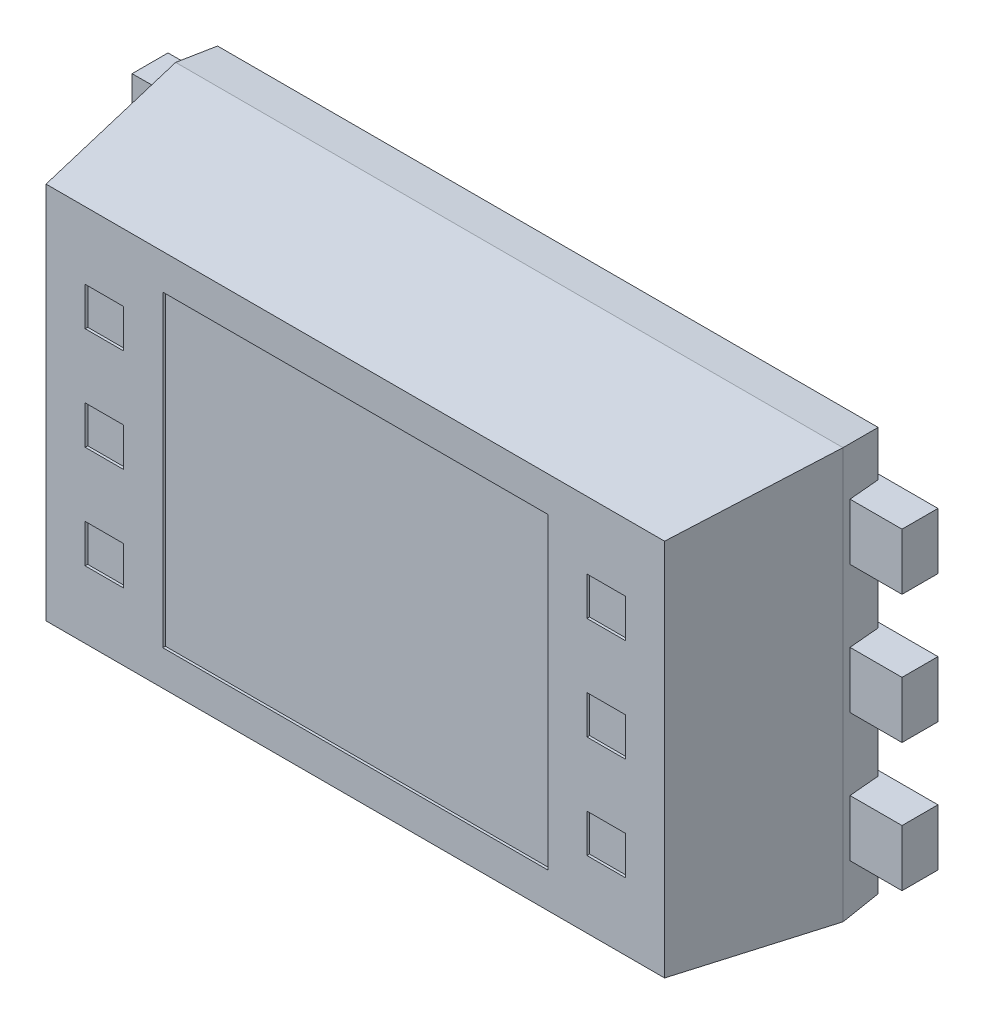
SolidWorks part; units mm, degrees
ref_plane "Спереди" through (0, 0, 0) normal (0, 0, 1) x (1, 0, 0)
ref_plane "Сверху" through (0, 0, 0) normal (0, 1, 0) x (1, 0, 0)
ref_plane "Справа" through (0, 0, 0) normal (1, 0, 0) x (0, 0, -1)
sketch "Эскиз1" plane through (0, 0, 0) normal (0, 0, 1) x (1, 0, 0)
  line L1 (0, 0) -> (2.6, 0)
  line L2 (0, 0) -> (0, 1.6)
  line L3 (0, 1.6) -> (2.6, 1.6)
  line L4 (2.6, 0) -> (2.6, 1.6)
  dimension "D1" = 2.6
  dimension "D2" = 1.6
extrude "Бобышка-Вытянуть1" add sketch "Эскиз1" along normal blind 0.6 and the other way blind 0.15 draft 5
chamfer "Фаска1" distance 0.6 angle 9 2 edges at (0, 0.8, 0.6) (2.6, 0.8, 0.6)
chamfer "Фаска2" distance 0.6 angle 6 2 edges at (1.3, 0, 0.6) (1.3, 1.6, 0.6)
sketch "Эскиз4" plane through (0, 0, -0.15) normal (0, 0, -1) x (-1, 0, 0)
  line L1 (-2.8, 0.8) -> (-2.8, 0.69)
  line L2 (-2.8, 0.69) -> (-2.53, 0.69)
  line L4 (-0.07, 0.41) -> (0.2, 0.41)
  line L5 (-2.8, 0.8) -> (-2.8, 0.91)
  line L6 (-2.53, 0.69) -> (-2.53, 0.91)
  line L7 (-2.53, 0.91) -> (-2.8, 0.91)
  line L9 (-2.8, 0.3) -> (-2.8, 0.19)
  line L10 (-2.8, 0.19) -> (-2.53, 0.19)
  line L11 (-2.8, 0.3) -> (-2.8, 0.41)
  line L12 (-2.53, 0.19) -> (-2.53, 0.41)
  line L13 (-2.53, 0.41) -> (-2.8, 0.41)
  line L14 (-0.07, 0.19) -> (-0.07, 0.41)
  line L15 (0.2, 0.3) -> (0.2, 0.41)
  line L16 (0.2, 0.19) -> (-0.07, 0.19)
  line L17 (0.2, 0.3) -> (0.2, 0.19)
  line L18 (-0.07, 0.91) -> (0.2, 0.91)
  line L19 (-0.07, 0.69) -> (-0.07, 0.91)
  line L20 (0.2, 0.8) -> (0.2, 0.91)
  line L21 (0.2, 0.69) -> (-0.07, 0.69)
  line L22 (0.2, 0.8) -> (0.2, 0.69)
  line L23 (-2.8, 1.3) -> (-2.8, 1.19)
  line L24 (-2.8, 1.19) -> (-2.53, 1.19)
  line L25 (-2.8, 1.3) -> (-2.8, 1.41)
  line L26 (-2.53, 1.19) -> (-2.53, 1.41)
  line L27 (-2.53, 1.41) -> (-2.8, 1.41)
  line L28 (-0.07, 1.4494) -> (-0.07, 1.1769)
  line L32 (0.2, 1.3119) -> (0.2, 1.1769)
  line L33 (0.2, 1.1769) -> (-0.07, 1.1769)
  line L34 (0.2, 1.3119) -> (0.2, 1.4469)
  line L35 (0.2, 1.4469) -> (-0.07, 1.4494)
  dimension "D1" = 2
  dimension "D2" = 2
extrude "Бобышка-Вытянуть2" add sketch "Эскиз4" against normal blind 0.12 and the other way blind 0.02
sketch "Эскиз5" plane through (0, 0, 0.6) normal (0, 0, 1) x (1, 0, 0)
  line L0 (0.2475, 1.275) -> (0.3975, 1.275)
  line L1 (2.2025, 0.875) -> (2.3525, 0.875)
  line L3 (0.2475, 1.275) -> (0.2475, 1.125)
  line L4 (0.2475, 1.125) -> (0.3975, 1.125)
  line L5 (0.55, 0.2) -> (2.05, 0.2)
  line L6 (0.55, 0.2) -> (0.55, 1.4)
  line L7 (0.55, 1.4) -> (2.05, 1.4)
  line L8 (2.05, 0.2) -> (2.05, 1.4)
  line L9 (0.55, 0.2) -> (2.05, 1.4) construction
  line L10 (0.55, 1.4) -> (2.05, 0.2) construction
  line L14 (2.2775, 0.2) -> (2.05, 0.2)
  line L15 (0.3975, 1.275) -> (0.3975, 1.125)
  line L16 (0.2475, 0.875) -> (0.3975, 0.875)
  line L17 (0.2475, 0.875) -> (0.2475, 0.725)
  line L18 (0.2475, 0.725) -> (0.3975, 0.725)
  line L19 (0.3975, 0.875) -> (0.3975, 0.725)
  line L20 (0.2475, 0.875) -> (0.3975, 0.725) construction
  line L21 (0.2475, 0.725) -> (0.3975, 0.875) construction
  line L22 (0.2475, 1.275) -> (0.3975, 1.125) construction
  line L23 (0.2475, 1.125) -> (0.3975, 1.275) construction
  line L24 (0.2475, 0.875) -> (0.3975, 0.875)
  line L25 (0.2475, 0.875) -> (0.2475, 0.725)
  line L26 (0.2475, 0.725) -> (0.3975, 0.725)
  line L27 (0.3975, 0.875) -> (0.3975, 0.725)
  line L28 (0.2475, 0.875) -> (0.3975, 0.725) construction
  line L29 (0.2475, 0.725) -> (0.3975, 0.875) construction
  line L30 (0.2475, 0.475) -> (0.3975, 0.475)
  line L31 (0.2475, 0.475) -> (0.2475, 0.325)
  line L32 (0.2475, 0.325) -> (0.3975, 0.325)
  line L33 (0.3975, 0.475) -> (0.3975, 0.325)
  line L34 (0.2475, 0.475) -> (0.3975, 0.325) construction
  line L35 (0.2475, 0.325) -> (0.3975, 0.475) construction
  line L37 (2.3525, 0.325) -> (2.2025, 0.475) construction
  line L38 (2.3525, 0.475) -> (2.2025, 0.325) construction
  line L39 (2.3525, 0.725) -> (2.2025, 0.875) construction
  line L40 (2.3525, 0.875) -> (2.2025, 0.725) construction
  line L41 (2.3525, 1.125) -> (2.2025, 1.275) construction
  line L42 (2.3525, 1.275) -> (2.2025, 1.125) construction
  line L43 (2.3525, 0.725) -> (2.2025, 0.875) construction
  line L44 (2.3525, 0.875) -> (2.2025, 0.725) construction
  line L45 (2.2025, 0.475) -> (2.2025, 0.325)
  line L46 (2.3525, 0.325) -> (2.2025, 0.325)
  line L47 (2.3525, 0.475) -> (2.3525, 0.325)
  line L48 (2.3525, 0.475) -> (2.2025, 0.475)
  line L53 (2.2025, 0.875) -> (2.2025, 0.725)
  line L54 (2.3525, 0.725) -> (2.2025, 0.725)
  line L55 (2.3525, 0.875) -> (2.3525, 0.725)
  line L57 (2.2025, 1.275) -> (2.2025, 1.125)
  line L58 (2.3525, 1.125) -> (2.2025, 1.125)
  line L59 (2.3525, 1.275) -> (2.3525, 1.125)
  line L60 (2.3525, 1.275) -> (2.2025, 1.275)
  point P5 (1.3, 0.8)
  point P6 (0.3225, 1.2)
  point P16 (0.3225, 0.8)
  point P25 (0.3225, 0.8)
  point P30 (0.3225, 0.4)
  point P46 (2.2775, 0.4)
  point P47 (2.2775, 0.8)
  point P48 (2.2775, 1.2)
  dimension "D1" = 1.5
  dimension "D2" = 1.2
  dimension "D3" = 0.15
  dimension "D4" = 0.15
  dimension "D6" = 2
  dimension "D5" = 2
extrude "Вырез-Вытянуть1" cut sketch "Эскиз5" against normal blind 0.01 contours L6 L5 L8 L7 | L0 L15 L4 L3 | L17 L16 L19 L18 | L30 L33 L32 L31 | L57 L58 L59 L60 | L45 L46 L47 L48 | L1 L55 L54 L53
